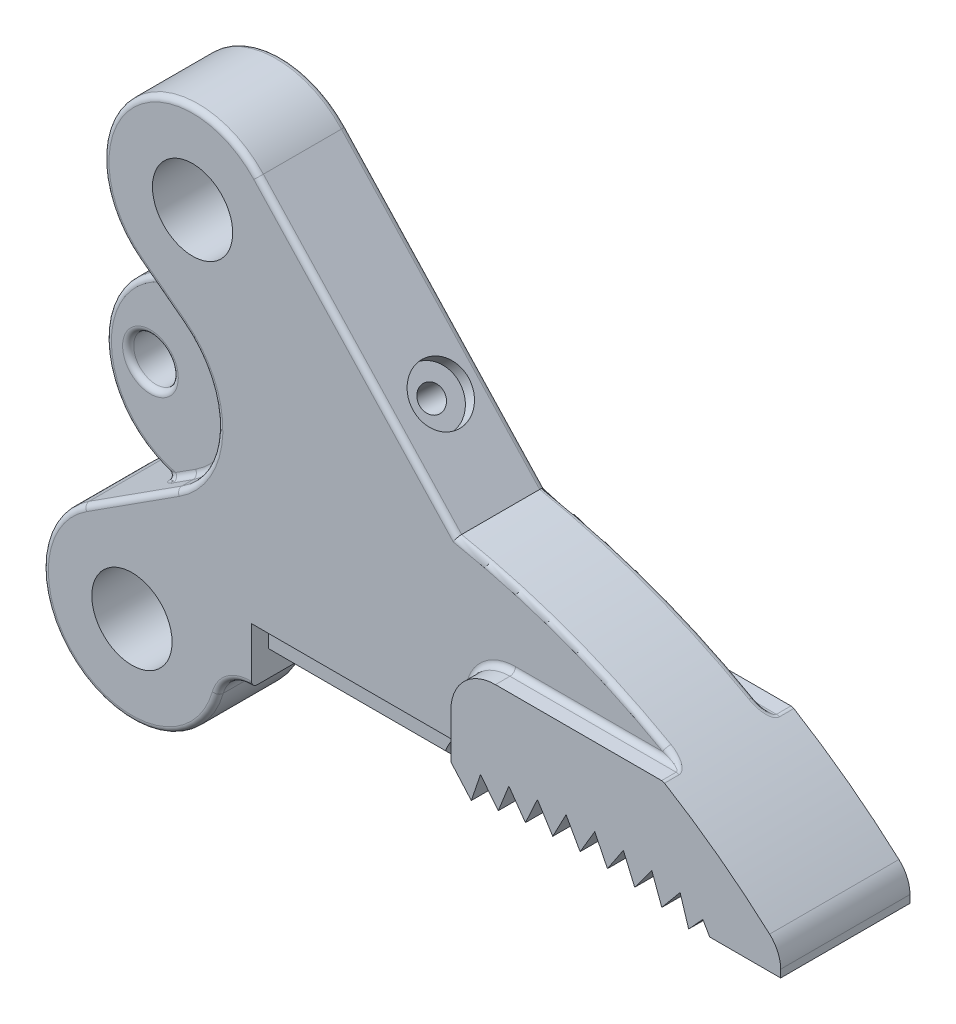
SolidWorks part; units mm, degrees
ref_plane "Front Plane" through (0, 0, 0) normal (0, 0, 1) x (1, 0, 0)
ref_plane "Top Plane" through (0, 0, 0) normal (0, 1, 0) x (1, 0, 0)
ref_plane "Right Plane" through (0, 0, 0) normal (1, 0, 0) x (0, 0, -1)
other "Configuration Table"
sketch "Sketch1" plane through (0, 0, 0) normal (0, 0, 1) x (1, 0, 0)
  line L0 (0, 0) -> (0, 50.8039) construction
  line L1 (0, 0) -> (47.4869, 47.4869) construction
  line L2 (0, 0) -> (-7.6716, 48.4365) construction
  line L3 (-24.9861, 25.7175) -> (66.7901, 25.7175) construction
  line L4 (-6.2085, 39.1989) -> (-4.0733, 25.7175)
  line L5 (-4.0733, 25.7175) -> (5.8796, 25.7175)
  line L6 (5.8796, 25.7175) -> (5.8796, 26.3525)
  line L7 (8.4196, 28.8925) -> (27.2088, 28.8925)
  circle A0 centre (0, 0) radius 39.6875 construction
  arc A1 (27.2088, 28.8925) -> (-6.2085, 39.1989) centre (0, 0) ccw
  arc A2 (8.4196, 28.8925) -> (5.8796, 26.3525) centre (8.4196, 26.3525) ccw
  point P16 (5.8796, 28.8925)
  dimension "D1" = 79.375
  dimension "D4" = 13.97
  dimension "D8" = 2.54
  dimension "D2" = 45
  dimension "D3" = 9
  dimension "D5" = 5.8796
  dimension "D6" = 3.175
  dimension "D7" = 21.3292
extrude "Extrude1" add sketch "Sketch1" along normal mid plane 3.175
sketch "Sketch2" plane through (0, 0, 0) normal (0, 0, 1) x (1, 0, 0)
  line L0 (8.4196, 28.8925) -> (-4.5761, 28.8925)
  line L4 (-6.2085, 39.1989) -> (-4.0733, 25.7175)
  line L5 (-4.0733, 25.7175) -> (5.8796, 25.7175)
  line L6 (5.8796, 25.7175) -> (5.8796, 26.3525)
  line L7 (8.4196, 28.8925) -> (27.2088, 28.8925)
  line L8 (-6.2085, 39.1989) -> (-4.5761, 28.8925)
  line L11 (8.4196, 28.8925) -> (27.2088, 28.8925)
  arc A2 (27.2088, 28.8925) -> (-6.2085, 39.1989) centre (0, 0) ccw
  arc A3 (8.4196, 28.8925) -> (5.8796, 26.3525) centre (8.4196, 26.3525) ccw
  arc A4 (27.2088, 28.8925) -> (-6.2085, 39.1989) centre (0, 0) ccw
  dimension "D1" = 0
extrude "Extrude2" add sketch "Sketch2" along normal mid plane 5.08
sketch "Sketch3" plane through (0, 0, 0) normal (0, 0, 1) x (1, 0, 0)
  line L2 (27.2088, 28.8925) -> (8.4196, 28.8925)
  line L4 (20.5175, 33.9725) -> (8.4196, 33.9725)
  line L5 (8.4196, 28.8925) -> (8.4196, 33.9725)
  arc A0 (27.2088, 28.8925) -> (-6.2085, 39.1989) centre (0, 0) ccw construction
  arc A1 (27.2088, 28.8925) -> (20.5175, 33.9725) centre (0, 0) ccw
  dimension "D1" = 5.08
extrude "Extrude3" add sketch "Sketch3" along normal mid plane 7.366
sketch "Sketch9" plane through (0, 0, 3.683) normal (0, 0, 1) x (1, 0, 0)
  line L0 (8.4196, 28.8925) -> (27.2088, 28.8925) construction
  line L1 (22.4336, 28.8925) -> (8.4196, 28.8925)
  arc A0 (8.4196, 28.8925) -> (22.4336, 28.8925) centre (15.4266, -1.6318) cw
  dimension "D1" = 31.3182
  dimension "D2" = 4.7752
extrude "Cut-Extrude1" cut sketch "Sketch9" against normal through all
sketch "Sketch4" plane through (0, 0, 0) normal (0, 0, 1) x (1, 0, 0)
  line L0 (8.4196, 28.8925) -> (9.5859, 27.5656)
  line L1 (9.5859, 27.5656) -> (10.1519, 29.239)
  line L3 (9.5859, 27.5656) -> (9.3525, 28.732) construction
  arc A1 (22.4336, 28.8925) -> (8.4196, 28.8925) centre (15.4266, -1.6318) ccw construction
  arc A2 (10.1519, 29.239) -> (8.4196, 28.8925) centre (15.4266, -1.6318) ccw
  dimension "D1" = 30
  dimension "D2" = 30
  dimension "D3" = 1.7666
extrude "Extrude4" add sketch "Sketch4" along normal up to surface and the other way up to surface up to face at (17.4268, 31.1188, 3.683) other way up to face at (17.4268, 31.1188, -3.683)
ref_axis "Axis1" through (15.4266, -1.6318, 3.683) along (0, 0, -1)
pattern_circular "CirPattern1" count 9 every 3 about axis through (15.4266, -1.6318, 3.683) along (0, 0, -1) of "Extrude4"
sketch "Sketch5" plane through (0, 28.8925, 0) normal (0, -1, 0) x (1, 0, 0)
  line L4 (22.4336, 3.683) -> (22.4336, -3.683)
  line L5 (22.4336, -3.683) -> (27.2088, -3.683)
  line L6 (27.2088, -3.683) -> (27.2088, 3.683)
  line L7 (27.2088, 3.683) -> (22.4336, 3.683)
  line L8 (22.4336, 3.683) -> (22.4336, -3.683)
  line L9 (22.4336, -3.683) -> (27.2088, -3.683)
  line L10 (27.2088, -3.683) -> (27.2088, 3.683)
  line L11 (27.2088, 3.683) -> (22.4336, 3.683)
  dimension "D1" = 0
extrude "Extrude5" add sketch "Sketch5" along normal blind 1.27
chamfer "Chamfer1" distance 1.27 angle 30 1 edges at (22.4336, 27.6225, 0) first distance on face at (22.4336, 27.773, 0)
sketch "Sketch6" plane through (0, 0, 0) normal (0, 0, 1) x (1, 0, 0)
  line L0 (27.2088, 27.6225) -> (-39.2014, 27.6225) construction
  line L1 (27.2088, 27.6225) -> (-26.6502, 58.718) construction
  line L2 (-13.6364, 29.9918) -> (-8.3623, 33.3792)
  line L3 (7.5756, 38.9578) -> (-3.7187, 51.0869)
  line L4 (-4.0733, 25.7175) -> (5.8796, 25.7175) construction
  line L5 (-5.8112, 25.7175) -> (-4.0733, 25.7175)
  line L6 (-4.0733, 25.7175) -> (-4.0733, 30.4299)
  line L7 (-4.0733, 30.4299) -> (23.8762, 30.4299)
  line L9 (23.8762, 30.4299) -> (23.8762, 27.6225)
  line L10 (23.8762, 27.6225) -> (27.2088, 27.6225)
  line L11 (-10.8912, 25.7175) -> (-11.2709, 46.6604) construction
  line L12 (27.2088, 28.8925) -> (27.2088, 27.6225)
  line L13 (27.2088, 27.6225) -> (27.2088, 28.8925) construction
  line L14 (-7.4365, 47.625) -> (-10.8912, 25.7175) construction
  line L15 (-8.0335, 41.6978) -> (-10.5106, 43.5807)
  circle A0 centre (-7.4365, 47.625) radius 2.286
  arc A2 (-13.6364, 29.9918) -> (-5.8112, 25.7175) centre (-10.8912, 25.7175) ccw
  circle A3 centre (-10.8912, 25.7175) radius 2.286
  arc A4 (20.5175, 33.9725) -> (-6.2085, 39.1989) centre (0, 0) ccw construction
  arc A5 (27.2088, 28.8925) -> (7.5756, 38.9578) centre (0, 0) ccw
  arc A6 (-3.7187, 51.0869) -> (-10.5106, 43.5807) centre (-7.4365, 47.625) ccw
  arc A8 (-8.3623, 33.3792) -> (-8.0335, 41.6978) centre (-11.1076, 37.6535) ccw
  dimension "D2" = 40.005
  dimension "D3" = 38.1
  dimension "D5" = 10.16
  dimension "D6" = 4.572
  dimension "D9" = 11.938
  dimension "D1" = 30
  dimension "D8" = 10
extrude "Extrude6" add sketch "Sketch6" along normal up to surface and the other way up to surface up to face at (5.4069, 33.4586, 2.54) other way up to face at (5.4069, 33.4586, -2.54)
sketch "Sketch7" plane through (0, 0, 0) normal (0, 0, 1) x (1, 0, 0)
  line L0 (-11.1076, 37.6535) -> (-6.0315, 37.4529) construction
  circle A1 centre (-11.1076, 37.6535) radius 1.27
  arc A2 (-8.3623, 33.3792) -> (-8.0335, 41.6978) centre (-11.1076, 37.6535) ccw construction
  circle A3 centre (-8.5695, 37.5532) radius 5.08
  dimension "D1" = 2.54
  dimension "D2" = 10.16
extrude "Extrude7" add sketch "Sketch7" along normal mid plane 2.54
fillet "Fillet5" radius 2.54 2 edges at (8.4196, 33.9725, -3.1115) (8.4196, 33.9725, 3.1115)
fillet "Fillet4" radius 0.3175 6 edges at (15.7385, 33.9725, 2.54) (8.4196, 30.1625, 2.54) (8.4196, 30.1625, -2.54) (15.7385, 33.9725, -2.54) (9.1635, 33.2286, -2.54) (9.1635, 33.2286, 2.54)
fillet "Fillet6" radius 0.635 2 edges at (2.1732, 28.8925, -1.5875) (2.1732, 28.8925, 1.5875)
fillet "Fillet7" radius 1.905 1 edges at (27.2088, 28.8925, 0)
fillet "Fillet10" radius 1.905 1 edges at (-5.8112, 25.7175, 0)
fillet "Fillet11" radius 0.3175 22 edges at (-4.1221, 25.7175, -2.54) (-5.3197, 25.3322, -2.54) (-13.917, 21.637, -2.54) (-10.9994, 31.6855, -2.54) (-6.0315, 37.4529, -2.54) (-9.272, 42.6393, -2.54) (-11.2034, 51.0334, -2.54) (20.5175, 33.9725, -3.2702) (20.4783, 33.9961, -2.7373) (-4.1221, 25.7175, 2.54) (-5.3197, 25.3322, 2.54) (-13.917, 21.637, 2.54) (-10.9994, 31.6855, 2.54) (-6.0315, 37.4529, 2.54) (-9.272, 42.6393, 2.54) (-11.2034, 51.0334, 2.54) (20.5175, 33.9725, 3.2702) (20.4507, 34.0128, 2.7028) (1.9284, 45.0223, -2.54) (13.9752, 37.1455, -2.54) (1.9284, 45.0223, 2.54) (13.9752, 37.1455, 2.54)
chamfer "Chamfer2" distance 1.4732 angle 45 2 edges at (0.9032, 25.7175, -1.5875) (0.9032, 25.7175, 1.5875)
fillet "Fillet12" radius 0.3175 12 edges at (-9.2106, 42.5926, 0) (-9.6064, 32.5802, 0) (-8.6221, 42.1452, -1.27) (-13.6456, 37.7539, -1.27) (-8.9844, 32.9797, -1.27) (-6.0315, 37.4529, -1.27) (-9.8376, 37.6535, -1.27) (-13.6456, 37.7539, 1.27) (-8.6221, 42.1452, 1.27) (-6.0315, 37.4529, 1.27) (-8.9844, 32.9797, 1.27) (-9.8376, 37.6535, 1.27)
hole_wizard "CBORE for #00 Binding Head Machine Screw1" positions "Sketch10" profile "Sketch11" counterbore size "#00" standard "ANSI Inch" end condition through all
sketch "Sketch10" plane through (-51.5088, 102.4093, 0) normal (0.7318, 0.6815, 0) x (0.6815, -0.7318, 0)
  point P0 (81.3755, 0.2182)
sketch "Sketch11" plane through (3.9465, 42.8551, -0.2182) normal (0, 0, 1) x (-0.6815, 0.7318, 0)
  line L0 (0, 0) -> (0, 29.7173)
  line L1 (0, 29.7173) -> (0.6985, 29.7173)
  line L2 (0.6985, 29.7173) -> (0.6985, 0.7112)
  line L3 (0.6985, 0.7112) -> (1.5875, 0.7112)
  line L4 (1.5875, 0.7112) -> (1.5875, 0)
  line L5 (1.5875, 0) -> (0, 0)
  line L6 (0, -6.35) -> (0, 107.95) construction
  dimension "Thru Hole Dia." = 1.397
  dimension "Thru Hole Depth" = 29.7173
  dimension "C'Bore Dia." = 3.175
  dimension "C'Bore Depth" = 0.7112
